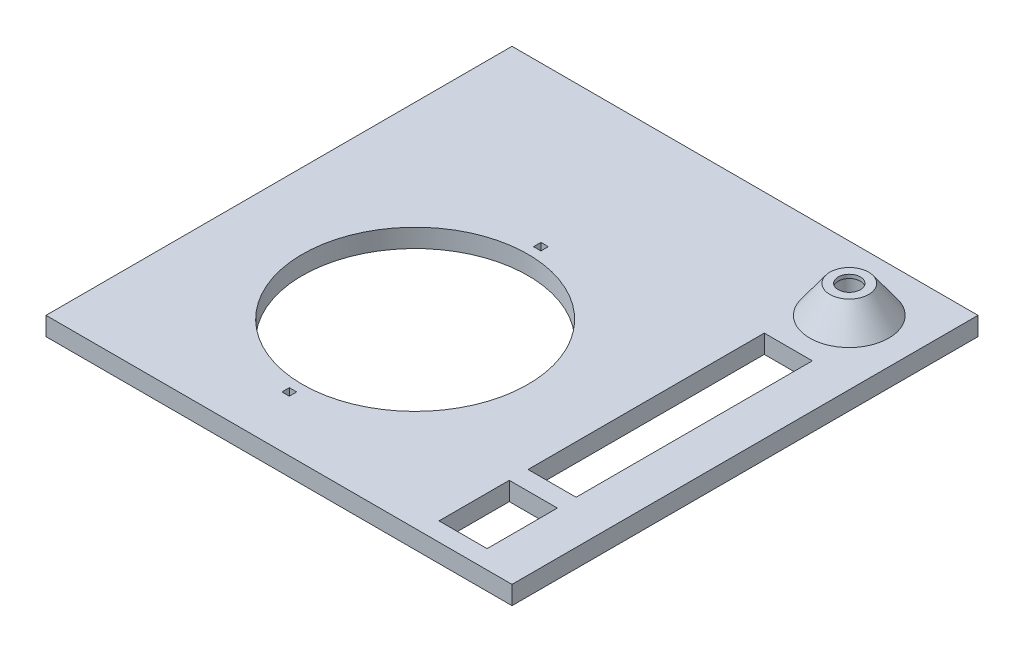
SolidWorks part; units mm, degrees
ref_plane "Front Plane" through (0, 0, 0) normal (0, 0, 1) x (1, 0, 0)
ref_plane "Top Plane" through (0, 0, 0) normal (0, 1, 0) x (1, 0, 0)
ref_plane "Right Plane" through (0, 0, 0) normal (1, 0, 0) x (0, 0, -1)
sketch "Sketch1" plane through (0, 0, 0) normal (0, 1, 0) x (1, 0, 0)
  line L1 (0, 0) -> (126, 0)
  line L2 (0, 0) -> (0, 126)
  line L3 (0, 126) -> (126, 126)
  line L4 (126, 0) -> (126, 126)
  dimension "D1" = 126
  dimension "D2" = 126
extrude "Boss-Extrude1" add sketch "Sketch1" along normal blind 5
sketch "Sketch3" plane through (0, 5, 0) normal (0, 1, 0) x (1, 0, 0)
  line L0 (108.6, 121.1) -> (108.6, 96.1) construction
  circle A0 centre (108.6, 108.6) radius 12.5
extrude "Boss-Extrude2" add sketch "Sketch3" along normal blind 7.5
sketch "Sketch4" plane through (0, 0, 0) normal (0, -1, 0) x (1, 0, 0)
  circle A1 centre (108.6, -108.6) radius 3.45
  dimension "D1" = 6.9
extrude "Cut-Extrude1" cut sketch "Sketch4" against normal blind 11.5
sketch "Sketch6" plane through (0, 12.5, 0) normal (0, 1, 0) x (1, 0, 0)
  line L0 (108.6, 121.1) -> (108.6, 96.1) construction
  circle A0 centre (108.6, 108.6) radius 12.5 construction
  circle A1 centre (108.6, 108.6) radius 3
  dimension "D1" = 6
extrude "Cut-Extrude2" cut sketch "Sketch6" against normal through all
chamfer "Chamfer1" distance 10 angle 36 1 edges at (108.6, 12.5, -96.1) first distance on face at (108.6, 12.5, -96.1)
sketch "Sketch8" plane through (0, 5, 0) normal (0, 1, 0) x (1, 0, 0)
  line L7 (114.2633, 24) -> (101.2633, 24)
  line L8 (114.2633, 24) -> (114.2633, 5)
  line L9 (114.2633, 5) -> (101.2633, 5)
  line L10 (101.2633, 24) -> (101.2633, 5)
  line L11 (114.2633, 24) -> (101.2633, 5) construction
  line L12 (114.2633, 5) -> (101.2633, 24) construction
  line L13 (114.2633, 24) -> (101.2633, 24)
  line L21 (114.2633, 29.0695) -> (101.2633, 29.0695)
  line L22 (114.2633, 29.0695) -> (114.2633, 92.9492)
  line L23 (114.2633, 92.9492) -> (101.2633, 92.9492)
  line L24 (101.2633, 29.0695) -> (101.2633, 92.9492)
  line L25 (114.2633, 29.0695) -> (101.2633, 92.9492) construction
  line L26 (114.2633, 92.9492) -> (101.2633, 29.0695) construction
  point P11 (107.7633, 14.5)
  point P17 (107.7633, 61.0093)
  dimension "D2" = 13
  dimension "D3" = 19
extrude "Cut-Extrude3" cut sketch "Sketch8" against normal through all contours L24 L21 L22 L23 | L7 L10 L9 L8 region at (107.7633, 5, -14.5) region at (107.7633, 5, -61.0093)
sketch "Sketch9" plane through (0, 5, 0) normal (0, 1, 0) x (1, 0, 0)
  circle A0 centre (50.8372, 48.9746) radius 30.5
  dimension "D1" = 61
extrude "Cut-Extrude4" cut sketch "Sketch9" against normal through all
sketch "Sketch10" plane through (0, 5, 0) normal (0, 1, 0) x (1, 0, 0)
  line L0 (50.8372, 79.4746) -> (50.8372, 18.4746) construction
  line L2 (18.3372, 67.7385) -> (18.3372, 30.2107)
  line L3 (18.3372, 30.2107) -> (50.8372, 11.4468)
  line L4 (50.8372, 11.4468) -> (83.3372, 30.2107)
  line L5 (83.3372, 30.2107) -> (83.3372, 67.7385)
  line L6 (83.3372, 67.7385) -> (50.8372, 86.5024)
  line L7 (50.8372, 86.5024) -> (18.3372, 67.7385)
  circle A0 centre (50.8372, 48.9746) radius 30.5 construction
  circle A1 centre (50.8372, 48.9746) radius 32.5 construction
  dimension "D1" = 65
sketch "Sketch11" plane through (0, 5, 0) normal (0, 1, 0) x (1, 0, 0)
  line L0 (50.8372, 79.4746) -> (50.8372, 86.5024) construction
  line L1 (50.8372, 11.4468) -> (50.8372, 18.4746) construction
  line L2 (51.8372, 83.9885) -> (49.8372, 83.9885)
  line L3 (51.8372, 83.9885) -> (51.8372, 81.9885)
  line L4 (51.8372, 81.9885) -> (49.8372, 81.9885)
  line L5 (49.8372, 83.9885) -> (49.8372, 81.9885)
  line L6 (51.8372, 83.9885) -> (49.8372, 81.9885) construction
  line L7 (51.8372, 81.9885) -> (49.8372, 83.9885) construction
  line L9 (51.8372, 13.9607) -> (49.8372, 13.9607)
  line L10 (51.8372, 13.9607) -> (51.8372, 15.9607)
  line L11 (51.8372, 15.9607) -> (49.8372, 15.9607)
  line L12 (49.8372, 13.9607) -> (49.8372, 15.9607)
  line L13 (51.8372, 13.9607) -> (49.8372, 15.9607) construction
  line L14 (51.8372, 15.9607) -> (49.8372, 13.9607) construction
  point P4 (50.8372, 82.9885)
  point P13 (50.8372, 14.9607)
  dimension "D1" = 2
  dimension "D2" = 2
  dimension "D3" = 2
  dimension "D4" = 2
extrude "Cut-Extrude5" cut sketch "Sketch11" against normal blind 3
sketch "Sketch13" plane through (0, 5, 0) normal (0, 1, 0) x (1, 0, 0)
  line L1 (126, 126) -> (0, 126) construction
  line L2 (50.8372, 126) -> (50.8372, 0) construction
  line L3 (0, 0) -> (126, 0) construction
  line L4 (0, 126) -> (0, 0) construction
  line L5 (0, 86.5024) -> (126, 86.5024) construction
  line L6 (126, 0) -> (126, 126) construction
  line L7 (18.3372, 126) -> (18.3372, 0) construction
  line L9 (83.3372, 126) -> (83.3372, 0) construction
